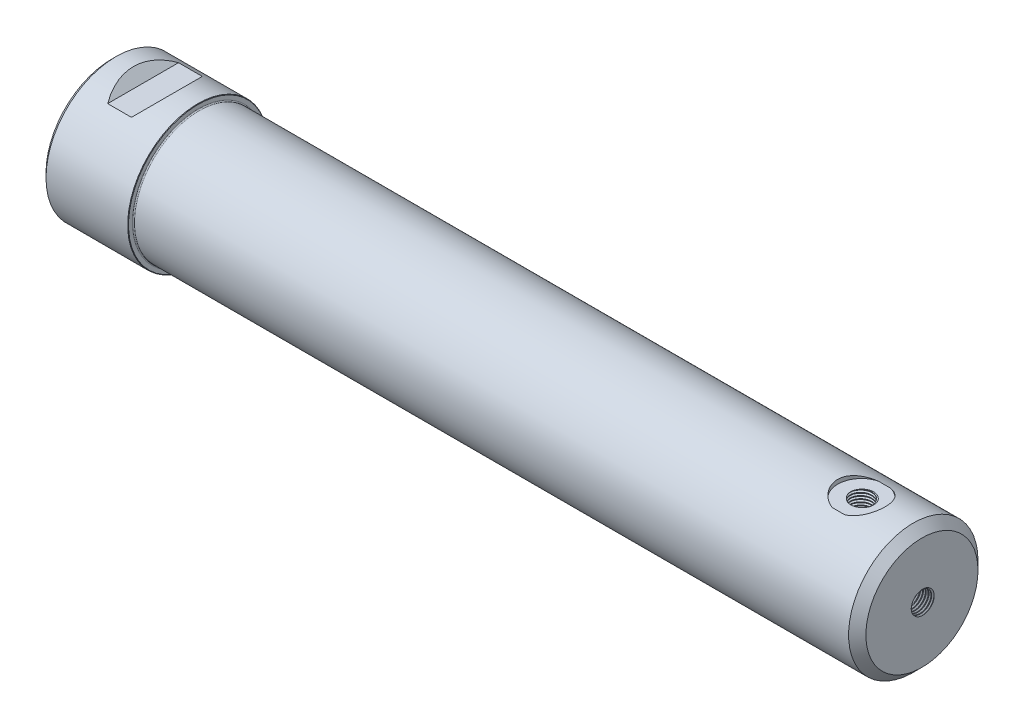
SolidWorks part; units mm, degrees
material "7075-T6 Aluminum"
ref_plane "Front Plane" through (0, 0, 0) normal (0, 0, 1) x (1, 0, 0)
ref_plane "Top Plane" through (0, 0, 0) normal (0, 1, 0) x (1, 0, 0)
ref_plane "Right Plane" through (0, 0, 0) normal (1, 0, 0) x (0, 0, -1)
sketch "Sketch1" plane through (0, 0, 0) normal (0, 1, 0) x (1, 0, 0)
  line L0 (-375.0129, 23.25) -> (-375.0129, 32.45)
  line L6 (-335.0129, 29.95) -> (-4, 29.95)
  line L8 (-25.0129, 15) -> (-328.6379, 15)
  line L9 (0, 0) -> (-375.0129, 0) construction
  line L10 (-25.0129, 15) -> (-16, 0)
  line L14 (-4, 29.95) -> (0, 25.95)
  line L15 (0, 25.95) -> (0, 0)
  line L16 (-16, 0) -> (0, 0)
  line L18 (-329.5129, 15.875) -> (-371.0129, 15.875)
  line L20 (-2, 27.95) -> (10.4366, 40.3866) construction
  line L21 (-335.0129, 29.95) -> (-335.0129, 32.45)
  line L22 (-335.0129, 32.45) -> (-375.0129, 32.45)
  line L23 (-371.0129, 15.875) -> (-371.0129, 23.25)
  line L24 (-371.0129, 23.25) -> (-375.0129, 23.25)
  line L29 (-329.5129, 15.875) -> (-328.6379, 15)
  dimension "D1" = 30
  dimension "D2" = 59.9
  dimension "D3" = 64.9
  dimension "D4" = 40
  dimension "D5" = 46.5
  dimension "D6" = 45
  dimension "D7" = 59
  dimension "D8" = 41.5
  dimension "D9" = 45
  dimension "D10" = 350
  dimension "D12" = 4
  dimension "D13" = 16
  dimension "D14" = 4
  dimension "D17" = 31.75
revolve "Revolve1" add sketch "Sketch1" angle 360 about L9
thread "Thread1" [suppressed] pitch 2 start angle 0, offset 12, length 45, pitch 2, diameter 49.822
ref_plane "Plane1" through (-275.3108, 0, -24.911) normal (0, -1, 0) x (0, 0, -1)
sketch "Thread Profile1" plane through (-275.3108, 0, -24.911) normal (0, -1, 0) x (0, 0, -1)
  line L0 (0, 0) -> (0, 2) construction
  line L11 (0, 0) -> (0, 1.75)
  line L12 (0, 1.75) -> (-1.0825, 1.125)
  line L13 (-1.0825, 1.125) -> (-1.0825, 0.625)
  line L15 (-1.0825, 0.625) -> (0, 0)
  line L17 (-1.0825, 0.875) -> (0, 0.875) construction
  point P2 (0, 0)
  dimension "Pitch" = 2
  dimension "Profile_Angle" = 60
  dimension "Profile_Land" = 0.5
  dimension "Profile_Height" = 1.0825
mirror "Mirror2" [suppressed]
sketch "Sketch2" [suppressed] plane through (0, 0, 0) normal (0, 1, 0) x (1, 0, 0)
  line L0 (-264.8108, 15.875) -> (-244.8108, 15.875)
  line L2 (-195.3108, 13.2) -> (-194.8108, 12.7)
  line L3 (-194.8108, 12.7) -> (-194.8108, 0)
  line L4 (-194.8108, 0) -> (-264.8108, 0)
  line L5 (-264.8108, 0) -> (-264.8108, 15.875)
  line L6 (0, 0) -> (-194.8108, 0) construction
  line L7 (-264.8108, 12.5) -> (-264.8108, -12.5) construction
  line L8 (-195.3108, 13.2) -> (-244.3108, 13.2)
  line L9 (-244.3108, 13.2) -> (-244.8108, 13.7)
  line L10 (-244.8108, 13.7) -> (-244.8108, 15.875)
  line L11 (-264.8108, 23.411) -> (-264.8108, -23.411) construction
  dimension "D1" = 31.75
  dimension "D2" = 25.4
  dimension "D3" = 45
  dimension "D4" = 70
  dimension "D5" = 0.5
  dimension "D6" = 20
fillet "Fillet1" [suppressed] radius 1.5
chamfer "Chamfer2" [suppressed] distance 0.2 angle 60
ref_plane "Plane2" through (-2, 0, -27.95) normal (0.7071, 0, -0.7071) x (-0.7071, 0, -0.7071)
sketch "Sketch10" plane through (-2, 0, -27.95) normal (0.7071, 0, -0.7071) x (-0.7071, 0, -0.7071)
  circle A0 centre (0, 0) radius 10
  dimension "D1" = 20
extrude "Cut-Extrude1" [suppressed] cut sketch "Sketch10" against normal blind 1.524
hole_wizard "7/16-20 Tapped Hole1" [suppressed] positions "Sketch11" profile "Sketch12" tap size "7/16-20" standard "ANSI Inch"
sketch "Sketch11" [suppressed] plane through (11.9224, 0, -11.9224) normal (0.7071, 0, -0.7071) x (-0.7071, 0, -0.7071)
  point P0 (21.2132, 0)
sketch "Sketch12" plane through (-3.0776, 0, -26.9224) normal (0, 1, 0) x (-0.7071, 0, -0.7071)
  line L0 (0, 0) -> (0, 39.0206)
  line L1 (0, 39.0206) -> (4.9606, 36.04)
  line L2 (4.9606, 36.04) -> (4.9606, 0)
  line L5 (4.9606, 0) -> (0, 0)
  line L10 (0, 39.0206) -> (-4.9606, 36.04) construction
  line L11 (0, -6.35) -> (0, 107.95) construction
  dimension "Tap Drill Dia." = 9.9212
  dimension "Tap Drill Depth" = 36.04
  dimension "Drill Angle" = 118
cosmetic thread "Hole Thread1" [suppressed] parameters "D1"=18.5333, "D2"=11.1125
mirror "Mirror3" [suppressed] about plane through (0, 0, 0) normal (0, 0, 1)
hole_wizard "7/16-20 Tapped Hole2" positions "Sketch13" profile "Sketch14" tap size "7/16-20" standard "ANSI Inch"
sketch "Sketch13" plane through (0, 0, 0) normal (1, 0, 0) x (0, 0, -1)
  point P0 (0, 0)
sketch "Sketch14" plane through (0, 0, 0) normal (0, 1, 0) x (0, 0, -1)
  line L0 (0, 0) -> (0, 29.0206)
  line L1 (0, 29.0206) -> (4.9606, 26.04)
  line L2 (4.9606, 26.04) -> (4.9606, 0)
  line L5 (4.9606, 0) -> (0, 0)
  line L10 (0, 29.0206) -> (-4.9606, 26.04) construction
  line L11 (0, -6.35) -> (0, 107.95) construction
  dimension "Tap Drill Dia." = 9.9212
  dimension "Tap Drill Depth" = 26.04
  dimension "Drill Angle" = 118
cosmetic thread "Hole Thread2" parameters "D1"=22.23, "D2"=11.1125
fillet "Fillet2" [suppressed] radius 3
sketch "Sketch15" plane through (0, 0, 0) normal (0, 1, 0) x (1, 0, 0)
  circle A0 centre (-28, 0) radius 11
  dimension "D1" = 22
  dimension "D2" = 28
extrude "Cut-Extrude2" cut sketch "Sketch15" along normal through all from offset 28
hole_wizard "7/16-20 Tapped Hole3" positions "Sketch16" profile "Sketch17" tap size "7/16-20" standard "ANSI Inch"
sketch "Sketch16" plane through (0, 28, 0) normal (0, 1, 0) x (1, 0, 0)
  point P0 (-28, 0)
sketch "Sketch17" plane through (-28, 28, 0) normal (1, 0, 0) x (0, 0, 1)
  line L0 (0, 0) -> (0, 29.0206)
  line L1 (0, 29.0206) -> (4.9606, 26.04)
  line L2 (4.9606, 26.04) -> (4.9606, 0)
  line L5 (4.9606, 0) -> (0, 0)
  line L10 (0, 29.0206) -> (-4.9606, 26.04) construction
  line L11 (0, -6.35) -> (0, 107.95) construction
  dimension "Tap Drill Dia." = 9.9212
  dimension "Tap Drill Depth" = 26.04
  dimension "Drill Angle" = 118
cosmetic thread "Hole Thread3" parameters "D1"=22.23, "D2"=11.1125
mirror "Mirror4" about plane through (0, 0, 0) normal (0, 1, 0) of "Cut-Extrude2", "7/16-20 Tapped Hole3"
chamfer "Chamfer3" [suppressed] distance 1 angle 45
sketch "Sketch18" [suppressed] plane through (-225.8108, 0, 0) normal (-1, 0, 0) x (0, 0, 1)
  line L0 (0, -25.4) -> (0, 0) construction
  line L1 (33.3067, 49.8795) -> (-33.3067, 49.8795)
  line L2 (33.3067, 49.8795) -> (33.3067, 25.4)
  line L3 (33.3067, 25.4) -> (-33.3067, 25.4)
  line L4 (-33.3067, 49.8795) -> (-33.3067, 25.4)
  line L5 (33.3067, 49.8795) -> (-33.3067, 25.4) construction
  line L6 (33.3067, 25.4) -> (-33.3067, 49.8795) construction
  line L7 (37.8978, -52.2323) -> (-37.8978, -52.2323)
  line L8 (37.8978, -52.2323) -> (37.8978, -25.4)
  line L9 (37.8978, -25.4) -> (-37.8978, -25.4)
  line L10 (-37.8978, -52.2323) -> (-37.8978, -25.4)
  line L11 (37.8978, -52.2323) -> (-37.8978, -25.4) construction
  line L12 (37.8978, -25.4) -> (-37.8978, -52.2323) construction
  line L13 (0, 0) -> (0, 25.4) construction
  point P0 (0, 37.6397)
  point P5 (0, -38.8162)
  dimension "D1" = 50.8
extrude "Cut-Extrude3" [suppressed] cut sketch "Sketch18" against normal blind 30
sketch "Sketch19" plane through (-375.0129, 0, 0) normal (-1, 0, 0) x (0, 0, 1)
  circle A0 centre (0, 0) radius 19 construction
  circle A1 centre (-19, 0) radius 2.4152
  dimension "D1" = 38
chamfer "Chamfer8" distance 0.2 angle 45 1 edges at (-375.0129, 0, -23.25)
chamfer "Chamfer9" distance 0.5 angle 45 1 edges at (-371.0129, 0, -15.875)
hole_wizard "M3x0.5 Tapped Hole1" positions "Sketch20" profile "Sketch21" tap size "M3x0.5" standard "ANSI Metric"
sketch "Sketch20" plane through (-371.0129, 0, 0) normal (-1, 0, 0) x (0, 0, 1)
  point P0 (-19, 0)
sketch "Sketch21" plane through (-371.0129, 0, -19) normal (0, 1, 0) x (0, 0, 1)
  line L0 (0, 0) -> (0, 8.2511)
  line L1 (0, 8.2511) -> (1.25, 7.5)
  line L2 (1.25, 7.5) -> (1.25, 0)
  line L5 (1.25, 0) -> (0, 0)
  line L10 (0, 8.2511) -> (-1.25, 7.5) construction
  line L11 (0, -6.35) -> (0, 107.95) construction
  dimension "Tap Drill Dia." = 2.5
  dimension "Tap Drill Depth" = 7.5
  dimension "Drill Angle" = 118
cosmetic thread "Hole Thread4" parameters "D1"=6, "D2"=3
pattern_circular "CirPattern1" count 3 over 360 about axis through (0, 0, 0) along (1, 0, 0) of "M3x0.5 Tapped Hole1"
sketch "Sketch22" plane through (0, 0, 0) normal (1, 0, 0) x (0, 0, -1)
  line L0 (0, 25.4) -> (0, 0) construction
  line L1 (-45.3926, 47.9128) -> (45.3926, 47.9128)
  line L2 (-45.3926, 47.9128) -> (-45.3926, 25.4)
  line L3 (-45.3926, 25.4) -> (45.3926, 25.4)
  line L4 (45.3926, 47.9128) -> (45.3926, 25.4)
  line L5 (-45.3926, 47.9128) -> (45.3926, 25.4) construction
  line L6 (-45.3926, 25.4) -> (45.3926, 47.9128) construction
  line L7 (-56.4043, -67.4891) -> (56.4043, -67.4891)
  line L8 (-56.4043, -67.4891) -> (-56.4043, -25.4)
  line L9 (-56.4043, -25.4) -> (56.4043, -25.4)
  line L10 (56.4043, -67.4891) -> (56.4043, -25.4)
  line L11 (-56.4043, -67.4891) -> (56.4043, -25.4) construction
  line L12 (-56.4043, -25.4) -> (56.4043, -67.4891) construction
  line L13 (0, 0) -> (0, -25.4) construction
  point P0 (0, 36.6564)
  point P5 (0, -46.4446)
  dimension "D1" = 50.8
extrude "Cut-Extrude4" [suppressed] cut sketch "Sketch22" against normal blind 16
fillet "Fillet3" [suppressed] radius 4
chamfer "Chamfer4" [suppressed] distance 1 angle 45
sketch "Sketch24" plane through (0, 0, 0) normal (0, 1, 0) x (1, 0, 0)
  line L0 (0, 0) -> (-274.4775, 0) construction
  line L1 (-274.1858, 23.8285) -> (-274.6858, 23.8285) construction
  point P3 (-274.4358, 23.8285)
  dimension "D1" = 47.6569
thread "Thread2" pitch 1.27 profile "Thread Profile3" start angle 0, offset 10, length 80, pitch 1.27, diameter 9.9212
ref_plane "Plane4" through (-32.9606, 38, 0) normal (0, 0, 1) x (-1, 0, 0)
sketch "Thread Profile3" plane through (-32.9606, 38, 0) normal (0, 0, 1) x (-1, 0, 0)
  line L0 (0, 0) -> (0, 1.27) construction
  line L1 (0, 0) -> (0.6874, 0.3969)
  line L2 (0.6874, 0.3969) -> (0.6874, 0.5556)
  line L3 (0.6874, 0.5556) -> (0, 0.9525)
  line L4 (0.6874, 0.4762) -> (0, 0.4762) construction
  line L11 (0, 0) -> (0, 0.9525)
  point P2 (0, 0)
  dimension "Pitch" = 1.27
  dimension "Profile_Angle" = 60
  dimension "Profile_Land" = 0.1588
  dimension "Profile_Height" = 0.6874
thread "Thread3" pitch 1.27 profile "Thread Profile4" start angle 0, offset 10, length 80, pitch 1.27, diameter 9.9212
ref_plane "Plane5" through (10, 0, 4.9606) normal (0, -1, 0) x (0, 0, 1)
sketch "Thread Profile4" plane through (10, 0, 4.9606) normal (0, -1, 0) x (0, 0, 1)
  line L0 (0, 0) -> (0, 1.27) construction
  line L1 (0, 0) -> (0.6874, 0.3969)
  line L2 (0.6874, 0.3969) -> (0.6874, 0.5556)
  line L3 (0.6874, 0.5556) -> (0, 0.9525)
  line L4 (0.6874, 0.4762) -> (0, 0.4762) construction
  line L11 (0, 0) -> (0, 0.9525)
  point P2 (0, 0)
  dimension "Pitch" = 1.27
  dimension "Profile_Angle" = 60
  dimension "Profile_Land" = 0.1588
  dimension "Profile_Height" = 0.6874
chamfer "Chamfer5" distance 0.2 angle 45 1 edges at (-335.0129, 0, -32.45)
fillet "Fillet4" radius 0.5 1 edges at (-335.0129, 0, -29.95)
chamfer "Chamfer6" distance 2 angle 45 1 edges at (-375.0129, 0, -32.45)
sketch "Sketch25" plane through (0, 0, 0) normal (0, 1, 0) x (1, 0, 0)
  line L0 (-375.0129, 0) -> (-335.0129, 0) construction
  line L1 (-365.0129, -29.9719) -> (-345.0129, -29.9719)
  line L2 (-365.0129, -29.9719) -> (-365.0129, 29.9719)
  line L3 (-365.0129, 29.9719) -> (-345.0129, 29.9719)
  line L4 (-345.0129, -29.9719) -> (-345.0129, 29.9719)
  line L5 (-365.0129, -29.9719) -> (-345.0129, 29.9719) construction
  line L6 (-365.0129, 29.9719) -> (-345.0129, -29.9719) construction
  line L8 (-375.0129, 30.45) -> (-375.0129, -30.45) construction
  line L9 (-335.0129, -32.25) -> (-335.0129, 32.25) construction
  point P0 (-355.0129, 0)
  dimension "D1" = 20
extrude "Cut-Extrude5" cut sketch "Sketch25" along normal through all from offset 28
chamfer "Chamfer7" distance 4.5 angle 45 2 edges at (-365.0129, 28, 0) (-345.0129, 28, 0)
mirror "Mirror5" about plane through (0, 0, 0) normal (0, 1, 0) of "Chamfer7", "Cut-Extrude5"
